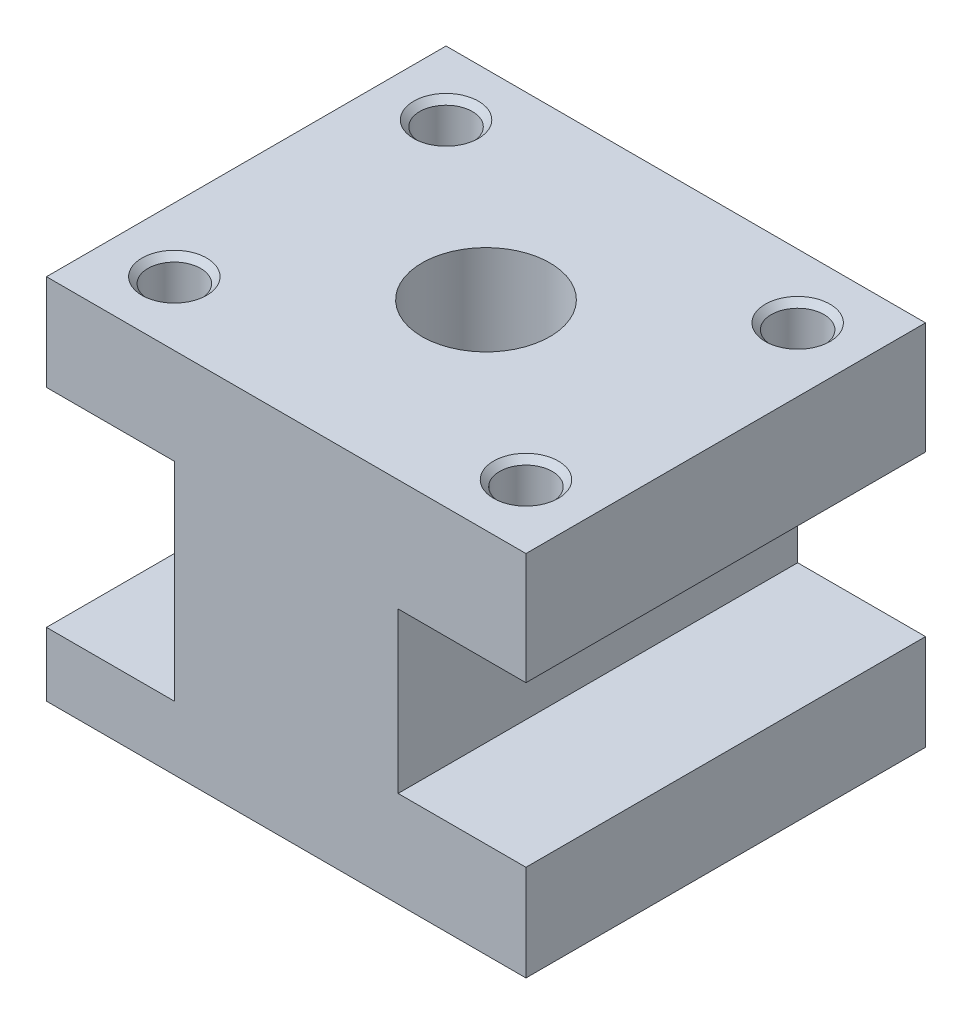
SolidWorks part; units mm, degrees
material "AISI 1020"
ref_plane "Plano frontal" through (0, 0, 0) normal (0, 0, 1) x (1, 0, 0)
ref_plane "Plano superior" through (0, 0, 0) normal (0, 1, 0) x (1, 0, 0)
ref_plane "Plano direito" through (0, 0, 0) normal (1, 0, 0) x (0, 0, -1)
sketch "Esboço1" plane through (0, 0, 0) normal (0, 0, 1) x (1, 0, 0)
  line L0 (-15, 0) -> (15, 0)
  line L1 (15, 0) -> (15, 6)
  line L2 (15, 6) -> (7, 6)
  line L3 (7, 6) -> (7, 16)
  line L4 (7, 16) -> (15, 16)
  line L5 (15, 16) -> (15, 23)
  line L6 (15, 23) -> (-15, 23)
  line L7 (-15, 23) -> (-15, 17)
  line L8 (-15, 17) -> (-7, 17)
  line L9 (-7, 17) -> (-7, 4)
  line L10 (-7, 4) -> (-15, 4)
  line L11 (-15, 4) -> (-15, 0)
  point P13 (0, 0)
  dimension "D1" = 30
  dimension "D2" = 23
  dimension "D3" = 10
  dimension "D4" = 13
  dimension "D5" = 8
  dimension "D6" = 4
  dimension "D7" = 6
  dimension "D8" = 8
extrude "Ressalto-extrusão1" add sketch "Esboço1" along normal mid plane 25
hole_wizard "Furo roscado de M4x0.71" positions "Esboço2" profile "Esboço3" tap size "M4x0.7" standard "Ansi Metric" end condition up to next
sketch "Esboço2" plane through (0, 23, 0) normal (0, 1, 0) x (1, 0, 0)
  line L0 (15, 12.5) -> (-15, 12.5) construction
  line L1 (-15, -12.5) -> (-15, 12.5) construction
  line L2 (0, 0) -> (0, 8.9806) construction
  point P0 (-11, 8.5)
  point P7 (11, 8.5)
  dimension "D1" = 4
  dimension "D2" = 4
sketch "Esboço3" plane through (-11, 23, -8.5) normal (1, 0, 0) x (0, 0, 1)
  line L0 (0, 0) -> (0, 23)
  line L1 (0, 23) -> (1.65, 23)
  line L2 (1.65, 23) -> (1.65, 0.375)
  line L3 (1.65, 0.375) -> (2.025, 0)
  line L5 (2.025, 0) -> (0, 0)
  line L6 (-1.65, 0.375) -> (-2.025, 0) construction
  line L11 (0, -6.35) -> (0, 107.95) construction
  dimension "Thru Tap Drill Dia." = 3.3
  dimension "Thru Tap Drill Depth" = 23
  dimension "Near C'Sink Dia." = 4.05
  dimension "Near C'Sink Angle" = 90
cosmetic thread "Rosca de furo1"
cosmetic thread "Rosca de furo2"
mirror "Espelhar1" about plane through (0, 0, 0) normal (0, 0, 1) of "Furo roscado de M4x0.71"
cosmetic thread "Rosca de furo3"
cosmetic thread "Rosca de furo4"
hole_wizard "Ø8.0mm Dowel Hole1" positions "Sketch1" profile "Sketch3" hole size "Ø8.0" standard "ANSI Metric" end condition through all
sketch "Sketch1" plane through (0, 23, 0) normal (0, 1, 0) x (1, 0, 0)
  point P0 (0, 0)
sketch "Sketch3" plane through (0, 23, 0) normal (1, 0, 0) x (0, 0, 1)
  line L0 (0, 0) -> (0, 23)
  line L1 (0, 23) -> (4, 23)
  line L2 (4, 23) -> (4, 0)
  line L5 (4, 0) -> (0, 0)
  line L11 (0, -6.35) -> (0, 107.95) construction
  dimension "Thru Hole Dia." = 8
  dimension "Thru Hole Depth" = 23
